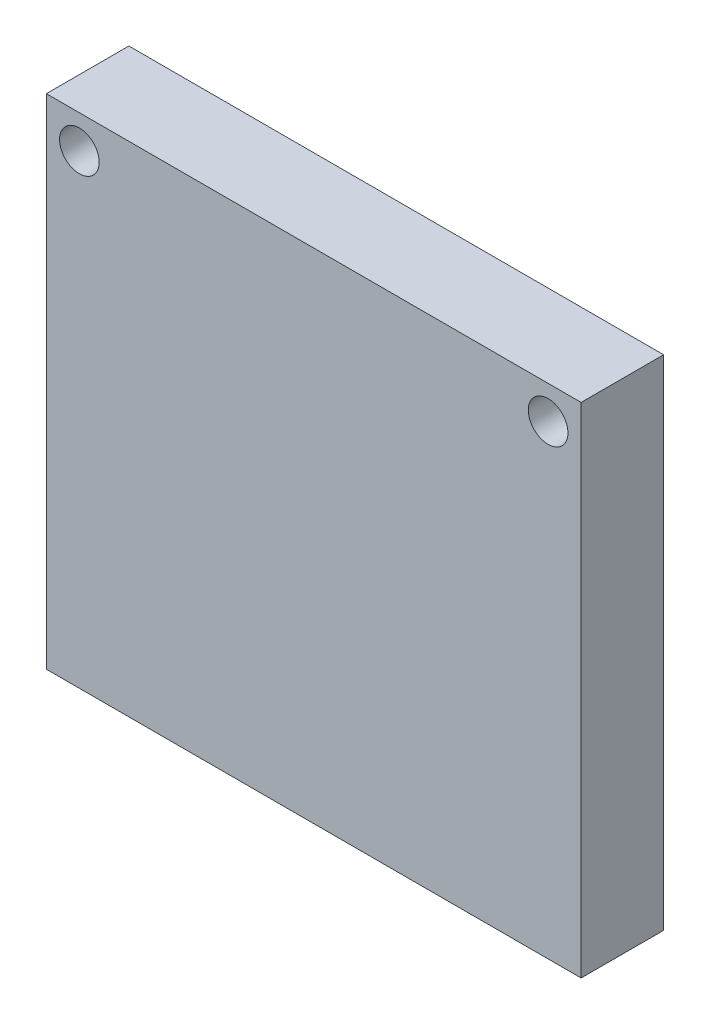
SolidWorks part; units mm, degrees
ref_plane "Front Plane" through (0, 0, 0) normal (0, 0, 1) x (1, 0, 0)
ref_plane "Top Plane" through (0, 0, 0) normal (0, 1, 0) x (1, 0, 0)
ref_plane "Right Plane" through (0, 0, 0) normal (1, 0, 0) x (0, 0, -1)
sketch "Sketch1" plane through (0, 0, 0) normal (0, 0, 1) x (1, 0, 0)
  line L1 (-8.1, 7.55) -> (8.1, 7.55)
  line L2 (-8.1, 7.55) -> (-8.1, -7.55)
  line L3 (-8.1, -7.55) -> (8.1, -7.55)
  line L4 (8.1, 7.55) -> (8.1, -7.55)
  line L5 (-8.1, 7.55) -> (8.1, -7.55) construction
  line L6 (-8.1, -7.55) -> (8.1, 7.55) construction
  point P0 (0, 0)
  dimension "D1" = 16.2
  dimension "D2" = 15.1
extrude "Boss-Extrude1" add sketch "Sketch1" along normal blind 2.5
hole_wizard "M1 Clearance Hole1" positions "Sketch2" profile "Sketch3" hole size "M1" standard "JIS"
sketch "Sketch2" plane through (0, 0, 2.5) normal (0, 0, 1) x (1, 0, 0)
  line L0 (8.1, -7.55) -> (8.1, 7.55) construction
  line L1 (8.1, 7.55) -> (-8.1, 7.55) construction
  point P0 (7.1, 6.55)
  dimension "D1" = 1
  dimension "D2" = 1
sketch "Sketch3" plane through (7.1, 6.55, 2.5) normal (1, 0, 0) x (0, -1, 0)
  line L0 (0, 0) -> (0, 3.5105)
  line L1 (0, 3.5105) -> (0.6, 3.15)
  line L2 (0.6, 3.15) -> (0.6, 0)
  line L5 (0.6, 0) -> (0, 0)
  line L10 (0, 3.5105) -> (-0.6, 3.15) construction
  line L11 (0, -6.35) -> (0, 107.95) construction
  dimension "Hole Dia." = 1.2
  dimension "Hole Depth" = 3.15
  dimension "Drill Angle" = 118
mirror "Mirror1" about plane through (0, 0, 0) normal (1, 0, 0) of "M1 Clearance Hole1"
